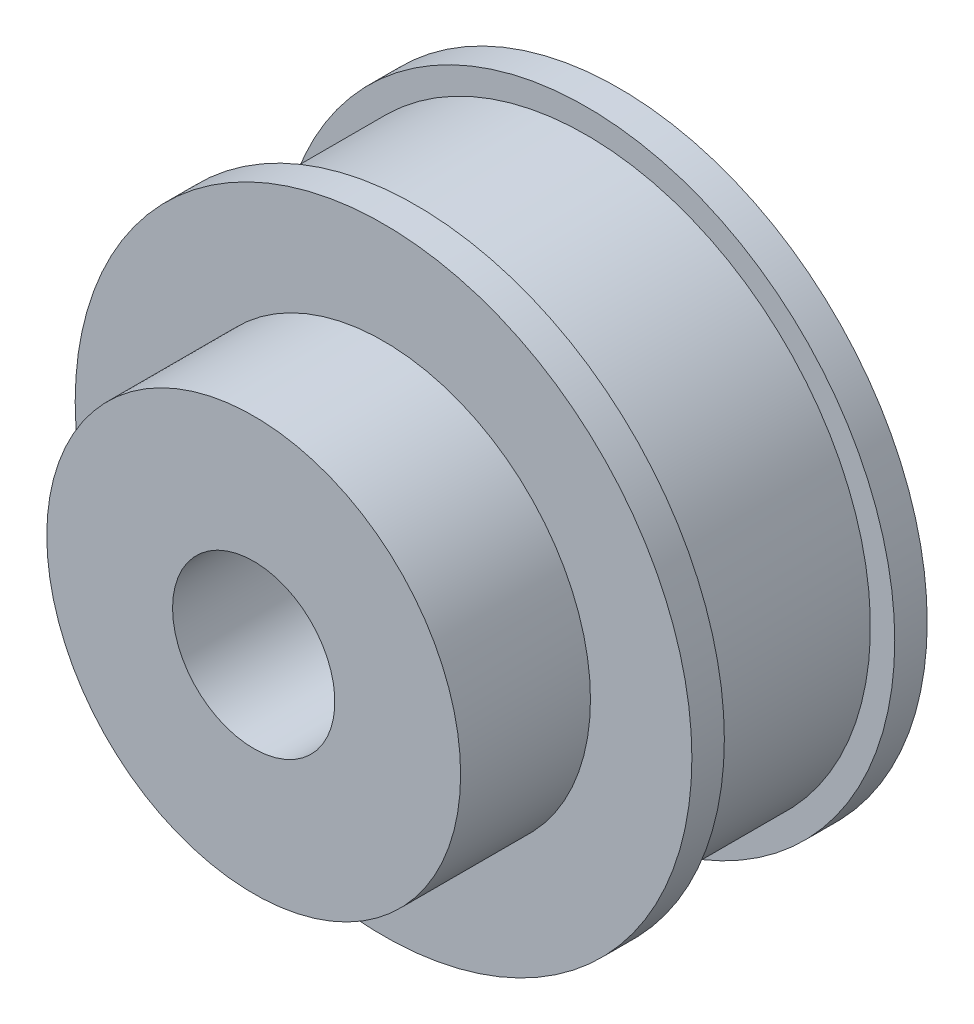
SolidWorks part; units mm, degrees
note: The reader was unsure of these and kept them because the rebuilt part matched: shared geometry of "Sketch3<2>".
ref_plane "Front Plane" through (0, 0, 0) normal (0, 0, 1) x (1, 0, 0)
ref_plane "Top Plane" through (0, 0, 0) normal (0, 1, 0) x (1, 0, 0)
ref_plane "Right Plane" through (0, 0, 0) normal (1, 0, 0) x (0, 0, -1)
sketch "Sketch1" plane through (0, 0, 0) normal (0, 0, 1) x (1, 0, 0)
  circle A0 centre (0, 0) radius 5
  circle A1 centre (0, 0) radius 17.5
  dimension "D1" = 35
  dimension "D2" = 10
extrude "Boss-Extrude1" add sketch "Sketch1" along normal blind 14.5
sketch "Sketch2" plane through (0, 0, 14.5) normal (0, 0, 1) x (1, 0, 0)
  circle A0 centre (0, 0) radius 12.75
  circle A1 centre (0, 0) radius 5
  dimension "D1" = 25.5
extrude "Boss-Extrude2" add sketch "Sketch2" along normal blind 8
sketch "Sketch3" plane through (0, 0, 0) normal (0, 0, -1) x (-1, 0, 0)
  circle A0 centre (0, 0) radius 19
  circle A1 centre (0, 0) radius 17.5
  dimension "D1" = 38
extrude "Boss-Extrude3" add sketch "Sketch3" against normal blind 2
extrude "Boss-Extrude5" add sketch "Sketch3<2>" along normal blind 2 from offset 14.5
sketch "Sketch3<2>" plane through (0, 0, 0) normal (0, 0, -1) x (-1, 0, 0) same geometry as "Sketch3"
